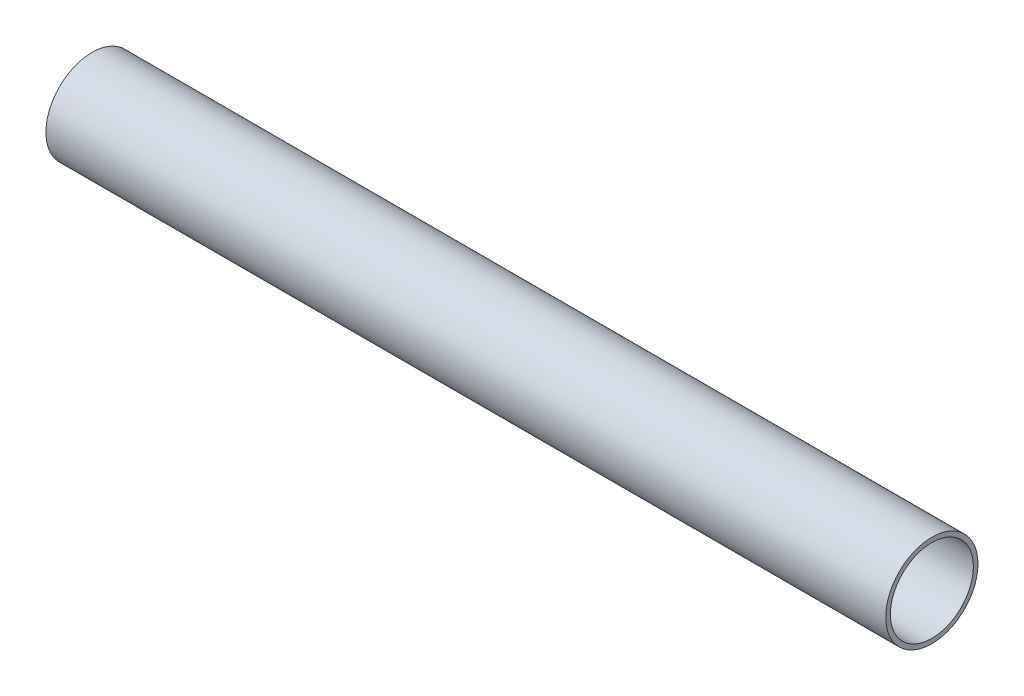
SolidWorks part; units mm, degrees
material "PC High Viscosity"
ref_plane "Front Plane" through (0, 0, 0) normal (0, 0, 1) x (1, 0, 0)
ref_plane "Top Plane" through (0, 0, 0) normal (0, 1, 0) x (1, 0, 0)
ref_plane "Right Plane" through (0, 0, 0) normal (1, 0, 0) x (0, 0, -1)
sketch "Sketch1" plane through (0, 0, 0) normal (1, 0, 0) x (0, 0, -1)
  circle A0 centre (0, 0) radius 15.875
  dimension "D1" = 31.75
extrude "Extrude-Thin1" add sketch "Sketch1" along normal mid plane 288.925 thin thin type one direction reverse wall 1.5875
